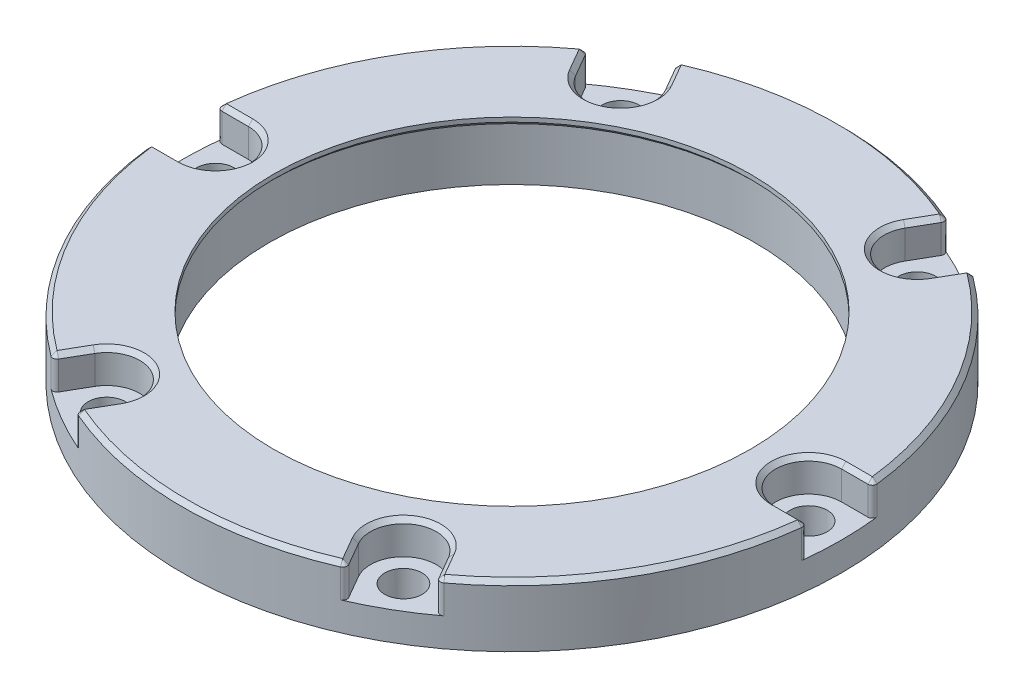
SolidWorks part; units mm, degrees
material "ABS"
ref_plane "Front Plane" through (0, 0, 0) normal (0, 0, 1) x (1, 0, 0)
ref_plane "Top Plane" through (0, 0, 0) normal (0, 1, 0) x (1, 0, 0)
ref_plane "Right Plane" through (0, 0, 0) normal (1, 0, 0) x (0, 0, -1)
sketch "Sketch5" plane through (0, 0, 0) normal (0, 0, 1) x (1, 0, 0)
  line L0 (0, 14.1349) -> (0, -4.8206) construction
  line L1 (0, 0) -> (22.1, 0) construction
  line L2 (22.1, 0) -> (30, 0)
  line L3 (22.1, 0) -> (22.1, 4.8)
  line L5 (30, 0) -> (30, 5.6)
  line L6 (22.1, 4.8) -> (21.7, 5.2)
  line L7 (21.7, 5.6) -> (30, 5.6)
  line L8 (21.7, 5.6) -> (21.7, 5.2)
  dimension "D1" = 4.8
  dimension "D2" = 22.1
  dimension "D3" = 30
  dimension "D4" = 5.6
  dimension "D5" = 45
  dimension "D6" = 0.4
revolve "Revolve1" add sketch "Sketch5" angle 360 about L0
hole_wizard "M3 Clearance Hole1" positions "Sketch2" profile "Sketch3" hole size "M3" standard "ISO" end condition through all
sketch "Sketch2" plane through (0, 5.6, 0) normal (0, 1, 0) x (1, 0, 0)
  line L0 (0, 0) -> (27, 0) construction
  point P0 (27, 0)
  dimension "D1" = 27
sketch "Sketch3" plane through (27, 5.6, 0) normal (1, 0, 0) x (0, 0, 1)
  line L0 (0, 0) -> (0, 5.6)
  line L1 (0, 5.6) -> (1.7, 5.6)
  line L2 (1.7, 5.6) -> (1.7, 0)
  line L5 (1.7, 0) -> (0, 0)
  line L11 (0, -6.35) -> (0, 107.95) construction
  dimension "Thru Hole Dia." = 3.4
  dimension "Thru Hole Depth" = 5.6
sketch "Sketch4" plane through (0, 5.6, 0) normal (0, 1, 0) x (1, 0, 0)
  line L0 (27, 3) -> (29.8496, 3)
  line L1 (27, -3) -> (29.8496, -3)
  arc A0 (27, 3) -> (27, -3) centre (27, 0) ccw
  arc A2 (29.8496, -3) -> (29.8496, 3) centre (0, 0) ccw
  circle A4 centre (0, 0) radius 30 construction
  dimension "D1" = 3
extrude "Cut-Extrude1" cut sketch "Sketch4" against normal blind 3
pattern_circular "CirPattern1" count 6 over 360 about axis through (0, 14.1349, 0) along (0, 1, 0) of "M3 Clearance Hole1", "Cut-Extrude1"
fillet "Fillet2" radius 0.4 12 edges at (-12.3267, 4.1, 27.3505) (-17.5229, 4.1, 24.3505) (-29.8496, 4.1, 3) (-29.8496, 4.1, -3) (-17.5229, 4.1, -24.3505) (-12.3267, 4.1, -27.3505) (12.3267, 4.1, -27.3505) (17.5229, 4.1, -24.3505) (29.8496, 4.1, -3) (29.8496, 4.1, 3) (12.3267, 4.1, 27.3505) (17.5229, 4.1, 24.3505)
chamfer "Chamfer1" distance 0.4 angle 45 36 edges at (-28.202, 5.6, 3) (-28.202, 5.6, -3) (-24, 5.6, 0) (-16.6991, 5.6, -22.9237) (-11.5029, 5.6, -25.9237) (-12, 5.6, -20.7846) (11.5029, 5.6, -25.9237) (16.6991, 5.6, -22.9237) (12, 5.6, -20.7846) (28.202, 5.6, -3) (28.202, 5.6, 3) (24, 5.6, 0) (16.6991, 5.6, 22.9237) (11.5029, 5.6, 25.9237) (12, 5.6, 20.7846) (-11.5029, 5.6, 25.9237) (-16.6991, 5.6, 22.9237) (-12, 5.6, 20.7846) (17.5654, 5.6, -24.1564) (12.1373, 5.6, -27.2903) (25.9808, 5.6, -15) (0, 5.6, -30) (29.7027, 5.6, -3.1339) (-12.1373, 5.6, -27.2903) (29.7027, 5.6, 3.1339) (-17.5654, 5.6, -24.1564) (25.9808, 5.6, 15) (-25.9808, 5.6, -15) (17.5654, 5.6, 24.1564) (-29.7027, 5.6, -3.1339) (12.1373, 5.6, 27.2903) (-29.7027, 5.6, 3.1339) (0, 5.6, 30) (-25.9808, 5.6, 15) (-12.1373, 5.6, 27.2903) (-17.5654, 5.6, 24.1564)
